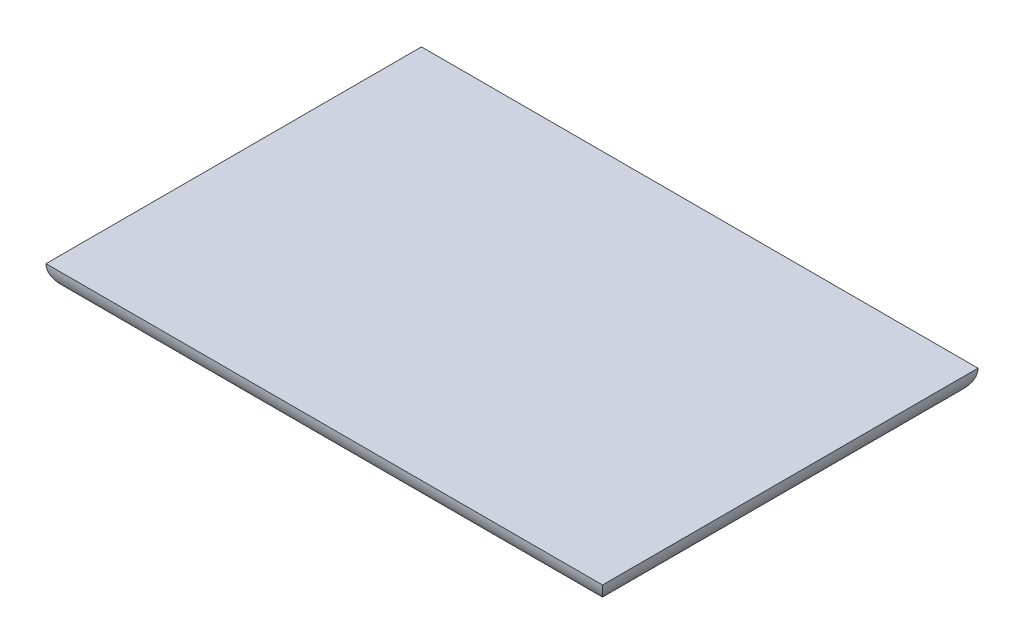
SolidWorks part; units mm, degrees
ref_plane "Front Plane" through (0, 0, 0) normal (0, 0, 1) x (1, 0, 0)
ref_plane "Top Plane" through (0, 0, 0) normal (0, 1, 0) x (1, 0, 0)
ref_plane "Right Plane" through (0, 0, 0) normal (1, 0, 0) x (0, 0, -1)
sketch "Sketch2" plane through (0, 0, 0) normal (0, 1, 0) x (1, 0, 0)
  line L1 (-207.5, -140) -> (207.5, -140)
  line L2 (-207.5, -140) -> (-207.5, 140)
  line L3 (-207.5, 140) -> (207.5, 140)
  line L4 (207.5, -140) -> (207.5, 140)
  line L5 (-207.5, -140) -> (207.5, 140) construction
  line L6 (-207.5, 140) -> (207.5, -140) construction
  point P0 (0, 0)
  dimension "D1" = 415
  dimension "D2" = 280
extrude "Boss-Extrude1" add sketch "Sketch2" along normal blind 19
fillet "Fillet1" radius 19 4 edges at (-207.5, 0, 0) (0, 0, -140) (207.5, 0, 0) (0, 0, 140)
